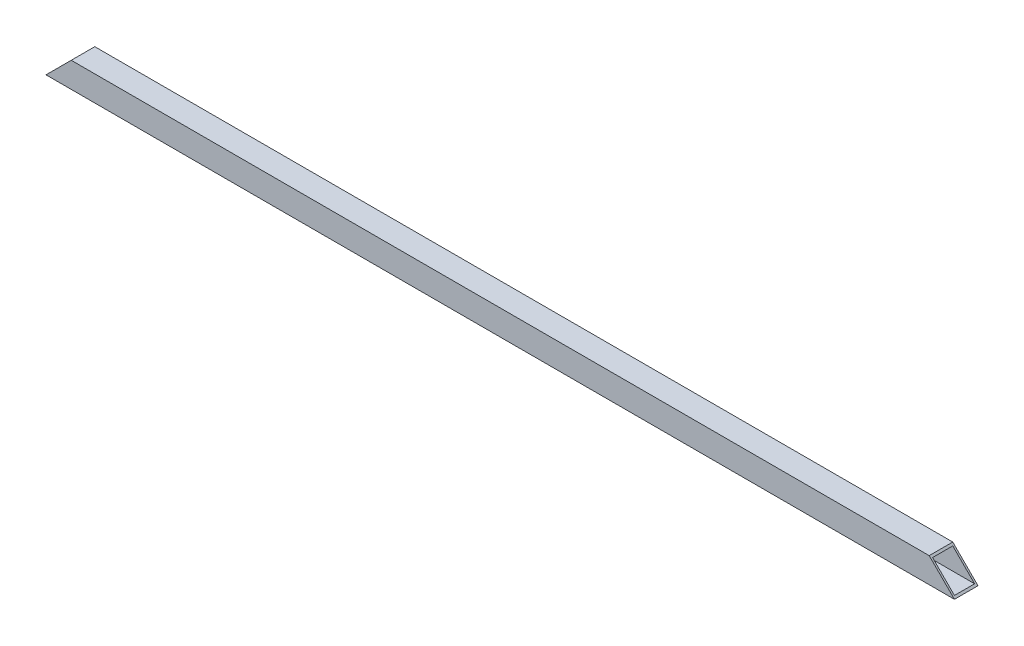
SolidWorks part; units mm, degrees
ref_plane "Спереди" through (0, 0, 0) normal (0, 0, 1) x (1, 0, 0)
ref_plane "Сверху" through (0, 0, 0) normal (0, 1, 0) x (1, 0, 0)
ref_plane "Справа" through (0, 0, 0) normal (1, 0, 0) x (0, 0, -1)
sketch "Эскиз2" plane through (0, 0, 0) normal (1, 0, 0) x (0, 0, -1)
  line L1 (-35, 37.5) -> (35, 37.5)
  line L2 (-35, 37.5) -> (-35, -37.5)
  line L3 (-35, -37.5) -> (35, -37.5)
  line L4 (35, 37.5) -> (35, -37.5)
  line L5 (-35, 37.5) -> (35, -37.5) construction
  line L6 (-35, -37.5) -> (35, 37.5) construction
  point P0 (0, 0)
extrude "Вытянуть-Тонкостенный1" add sketch "Эскиз2" along normal blind 2700 thin thin type one direction reverse wall 5
sketch "Эскиз3" plane through (0, 0, -35) normal (0, 0, -1) x (-1, 0, 0)
  line L0 (-2700, -37.5) -> (-2625, 37.5)
  line L1 (-2700, 37.5) -> (0, 37.5) construction
  line L2 (-2625, 37.5) -> (-75, 37.5)
  line L3 (-75, 37.5) -> (0, -37.5)
  line L4 (0, -37.5) -> (-2700, -37.5)
extrude "Вырез-Вытянуть1" cut sketch "Эскиз3" against normal through all flip side to cut
